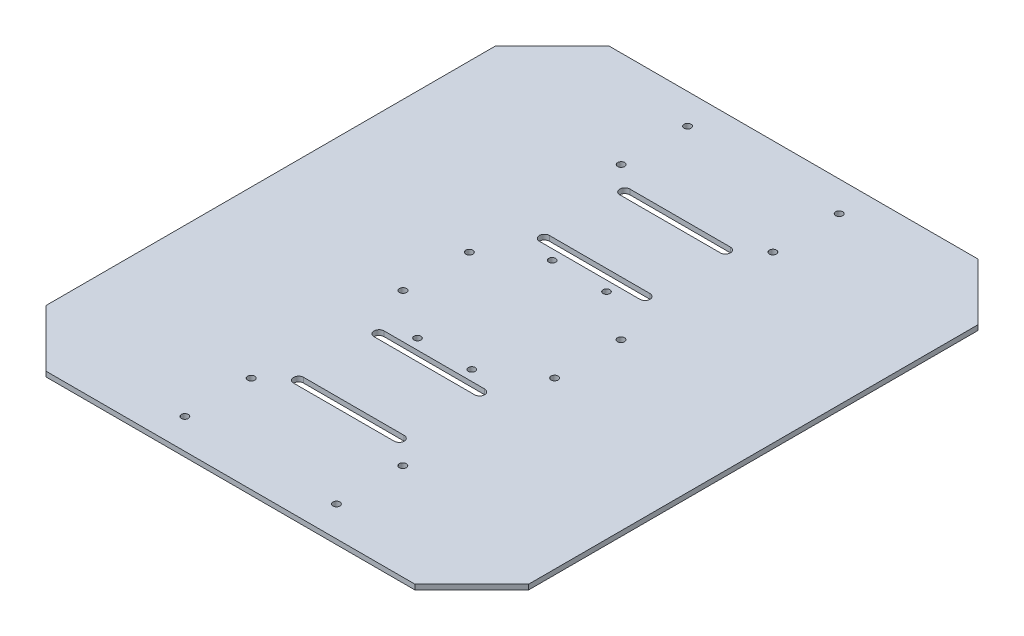
SolidWorks part; units mm, degrees
ref_plane "Front Plane" through (0, 0, 0) normal (0, 0, 1) x (1, 0, 0)
ref_plane "Top Plane" through (0, 0, 0) normal (0, 1, 0) x (1, 0, 0)
ref_plane "Right Plane" through (0, 0, 0) normal (1, 0, 0) x (0, 0, -1)
sketch "Sketch1" plane through (0, 0, 0) normal (0, 1, 0) x (1, 0, 0)
  line L0 (-121.2861, 87.138) -> (-85.365, 123.059)
  line L1 (-121.2861, 123.059) -> (183.5139, 123.059)
  line L2 (-121.2861, 123.059) -> (-121.2861, -232.541)
  line L3 (-121.2861, -232.541) -> (183.5139, -232.541)
  line L4 (183.5139, 123.059) -> (183.5139, -232.541)
  line L5 (31.1139, 95.069) -> (31.1139, -294.9418) construction
  line L6 (-146.0448, -54.741) -> (218.038, -54.741) construction
  line L7 (183.5139, 87.138) -> (147.5929, 123.059)
  line L8 (183.5139, -196.62) -> (147.5929, -232.541)
  line L9 (-121.2861, -196.62) -> (-85.365, -232.541)
  circle A0 centre (-16.7651, 104.009) radius 2.2225
  circle A1 centre (78.9929, 104.009) radius 2.2225
  circle A2 centre (-16.7651, 62.099) radius 2.2225
  circle A3 centre (78.9929, 62.099) radius 2.2225
  circle A4 centre (-16.7651, -171.581) radius 2.2225
  circle A5 centre (78.9929, -171.581) radius 2.2225
  circle A6 centre (78.9929, -213.491) radius 2.2225
  circle A7 centre (-16.7651, -213.491) radius 2.2225
  circle A8 centre (-16.7651, -33.786) radius 2.2225
  circle A9 centre (78.9929, -33.786) radius 2.2225
  circle A10 centre (78.9929, -75.696) radius 2.2225
  circle A11 centre (-16.7651, -75.696) radius 2.2225
  point P8 (31.1139, 123.059)
  point P11 (-121.2861, -54.741)
  dimension "D6" = 95.758
  dimension "D13" = 4.445
  dimension "D1" = 304.8
  dimension "D2" = 355.6
  dimension "D3" = 45
  dimension "D4" = 50.8
  dimension "D5" = 41.91
  dimension "D7" = 104.521
  dimension "D8" = 19.05
  dimension "D9" = 41.91
  dimension "D10" = 20.955
  dimension "D11" = 95.758
  dimension "D12" = 47.879
extrude "Boss-Extrude1" add sketch "Sketch1" along normal blind 3.175 contours L2 L9 L3 L8 L4 L7 L1 L0 region at (31.1139, 0, 54.741)
sketch "Sketch2" plane through (0, 3.175, 0) normal (0, 1, 0) x (1, 0, 0)
  line L0 (31.1139, 123.059) -> (31.1139, -287.8465) construction
  line L1 (-85.365, 123.059) -> (147.5929, 123.059) construction
  line L2 (183.5139, -54.741) -> (-158.2106, -54.741) construction
  line L3 (183.5139, 87.138) -> (183.5139, -196.62) construction
  circle A0 centre (13.8419, -12.069) radius 2.159
  circle A1 centre (48.1319, -12.069) radius 2.159
  circle A2 centre (13.8419, -97.159) radius 2.159
  circle A3 centre (48.1319, -97.159) radius 2.159
  dimension "D5" = 4.318
  dimension "D6" = 4.318
  dimension "D7" = 4.318
  dimension "D8" = 4.318
  dimension "D1" = 17.272
  dimension "D2" = 34.29
  dimension "D3" = 85.09
  dimension "D4" = 42.672
extrude "Cut-Extrude1" cut sketch "Sketch2" against normal through all
sketch "Sketch4" plane through (0, 3.175, 0) normal (0, 1, 0) x (1, 0, 0)
  line L0 (-0.6361, 48.256) -> (62.8639, 48.256) construction
  line L1 (-0.6361, 51.431) -> (62.8639, 51.431)
  line L2 (-0.6361, 45.081) -> (62.8639, 45.081)
  line L3 (-0.6361, -2.544) -> (62.8639, -2.544) construction
  line L4 (-0.6361, 0.631) -> (62.8639, 0.631)
  line L5 (-0.6361, -5.719) -> (62.8639, -5.719)
  line L6 (31.1139, 123.059) -> (31.1139, -75.2432) construction
  line L7 (-85.365, 123.059) -> (147.5929, 123.059) construction
  line L8 (-121.2861, -54.741) -> (257.7387, -54.741) construction
  line L9 (-121.2861, 87.138) -> (-121.2861, -196.62) construction
  line L10 (31.1139, -232.541) -> (31.1139, -34.2388) construction
  line L11 (-0.6361, -106.938) -> (62.8639, -106.938) construction
  line L12 (-0.6361, -110.113) -> (62.8639, -110.113)
  line L13 (-0.6361, -103.763) -> (62.8639, -103.763)
  line L14 (-0.6361, -157.738) -> (62.8639, -157.738) construction
  line L15 (-0.6361, -160.913) -> (62.8639, -160.913)
  line L16 (-0.6361, -154.563) -> (62.8639, -154.563)
  arc A0 (-0.6361, 51.431) -> (-0.6361, 45.081) centre (-0.6361, 48.256) ccw
  arc A1 (62.8639, 45.081) -> (62.8639, 51.431) centre (62.8639, 48.256) ccw
  arc A2 (-0.6361, 0.631) -> (-0.6361, -5.719) centre (-0.6361, -2.544) ccw
  arc A3 (62.8639, -5.719) -> (62.8639, 0.631) centre (62.8639, -2.544) ccw
  circle A4 centre (48.1319, -12.069) radius 2.159 construction
  arc A5 (-0.6361, -110.113) -> (-0.6361, -103.763) centre (-0.6361, -106.938) cw
  arc A6 (62.8639, -103.763) -> (62.8639, -110.113) centre (62.8639, -106.938) cw
  arc A7 (-0.6361, -160.913) -> (-0.6361, -154.563) centre (-0.6361, -157.738) cw
  arc A8 (62.8639, -154.563) -> (62.8639, -160.913) centre (62.8639, -157.738) cw
  point P2 (31.1139, 48.256)
  point P7 (31.1139, -2.544)
  point P28 (31.1139, -106.938)
  point P35 (31.1139, -157.738)
  dimension "D1" = 63.5
  dimension "D2" = 63.5
  dimension "D3" = 6.35
  dimension "D4" = 6.35
  dimension "D5" = 44.45
  dimension "D6" = 6.35
extrude "Cut-Extrude2" cut sketch "Sketch4" against normal through all
